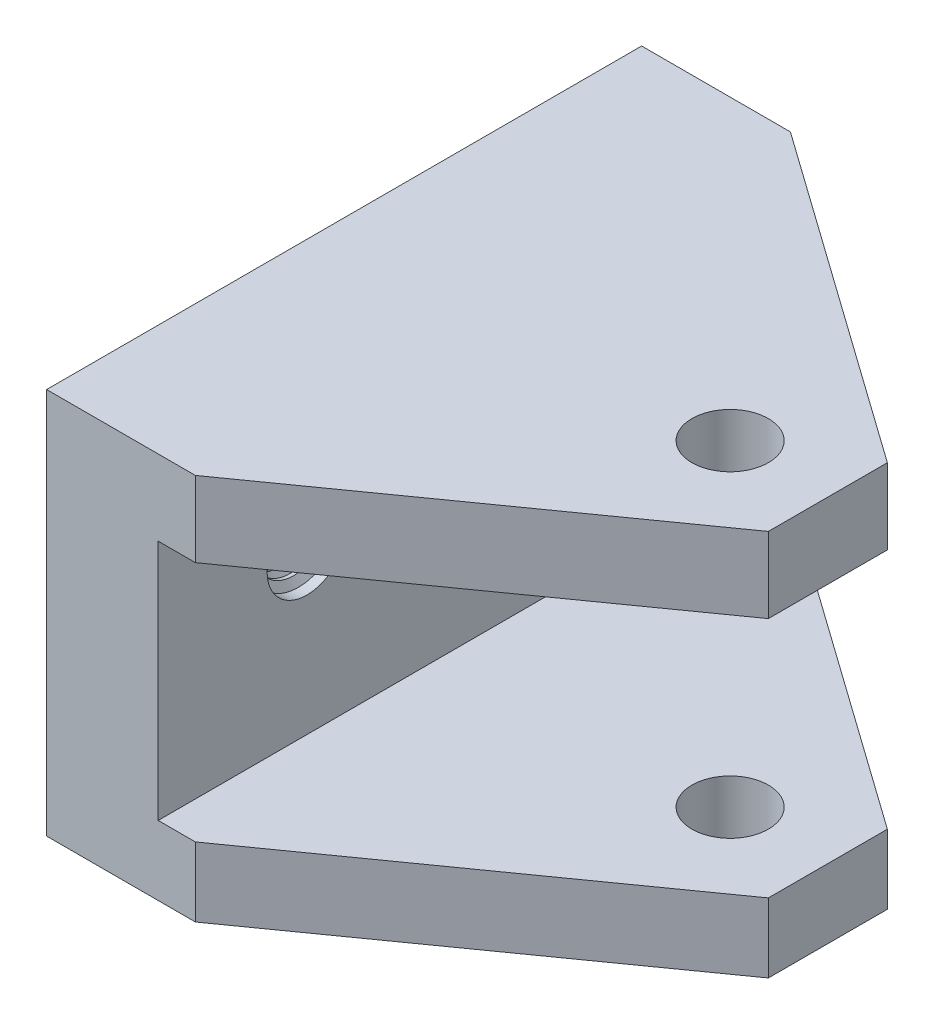
SolidWorks part; units mm, degrees
material "Custom Plastic"
ref_plane "X-Y Datum" through (0, 0, 0) normal (0, 0, 1) x (1, 0, 0)
ref_plane "X-Z Datum" through (0, 0, 0) normal (0, 1, 0) x (1, 0, 0)
ref_plane "Y-Z Datum" through (0, 0, 0) normal (1, 0, 0) x (0, 0, -1)
sketch "Sketch1" plane through (0, 0, 0) normal (0, 0, 1) x (1, 0, 0)
  line L0 (0, 1.7916) -> (0, 34.8116)
  line L1 (0, 34.8116) -> (45.6553, 34.8116)
  line L2 (45.6553, 34.8116) -> (45.6553, 28.3637)
  line L3 (45.6553, 28.3637) -> (9.525, 28.3637)
  line L4 (9.525, 28.3637) -> (9.525, 7.7135)
  line L5 (9.525, 7.7135) -> (45.6553, 7.7135)
  line L6 (45.6553, 7.7135) -> (45.6553, 1.7916)
  line L7 (0, 1.7916) -> (45.6553, 1.7916)
  line L8 (32.9553, 34.8116) -> (32.9553, 1.7916) construction
  line L9 (0, 21.4305) -> (9.525, 21.4305) construction
  line L10 (-200003.822, 21.4305) -> (200058.8771, 21.4305) construction
  line L11 (0, -10.6311) -> (0, 37.657) construction
  circle A0 centre (32.9553, 18.0386) radius 10.3251 construction
  dimension "D3" = 20.6502
  dimension "D1" = 20.6502
  dimension "D2" = 33.02
  dimension "D4" = 12.7
  dimension "D5" = 9.525
extrude "Boss-Extrude1" add sketch "Sketch1" along normal blind 50.8
sketch "Sketch2" plane through (9.525, 0, 0) normal (1, 0, 0) x (0, 0, -1)
  line L0 (-25.4, 28.3637) -> (-25.4, 7.7135) construction
  line L1 (-50.8, 28.3637) -> (0, 28.3637) construction
  line L2 (-50.8, 7.7135) -> (0, 7.7135) construction
  line L3 (-38.1, 21.4305) -> (-12.7, 21.4305) construction
  line L4 (-12.7, 21.4305) -> (0, 21.4305) construction
  line L6 (0, 28.3637) -> (0, 7.7135) construction
  circle A0 centre (-38.1, 21.4305) radius 3.4
  circle A1 centre (-12.7, 21.4305) radius 3.4
  dimension "D1" = 6.8
  dimension "D2" = 25.4
  dimension "D3" = 12.7
extrude "Cut-Extrude1" cut sketch "Sketch2" against normal blind 50.8
sketch "Sketch3" plane through (0, 34.8116, 0) normal (0, 1, 0) x (1, 0, 0)
  line L0 (0, -25.4) -> (45.6553, -25.4) construction
  line L1 (0, -50.8) -> (0, 0) construction
  line L2 (45.6553, -50.8) -> (45.6553, 0) construction
  line L3 (12.7, 0) -> (41.2992, -20.32)
  line L4 (41.2992, -20.32) -> (41.2992, -30.48)
  line L5 (41.2992, -30.48) -> (12.7, -50.8)
  line L6 (45.6553, -50.8) -> (0, -50.8) construction
  line L7 (12.7, -50.8) -> (45.6553, -50.8)
  line L8 (45.6553, -50.8) -> (45.6553, 0)
  line L9 (45.6553, 0) -> (12.7, 0)
  line L10 (45.6553, 0) -> (0, 0) construction
  circle A0 centre (32.9553, -25.4) radius 3.2639
  point P7 (45.6553, -25.4)
  dimension "D1" = 6.5278
  dimension "D5" = 5.08
  dimension "D2" = 12.7
  dimension "D3" = 10.16
  dimension "D4" = 12.7
extrude "Cut-Extrude2" cut sketch "Sketch3" against normal up to surface (33.02 mm away) up to face at (22.8276, 1.7916, 25.4)
thread "Thread1" pitch 1.25 method extrude profile "Thread Profile1" start angle 0, offset 0, length 0, pitch 1.25, diameter 6.8
ref_plane "Plane1" through (9.525, 21.4305, 16.1) normal (0, -1, 0) x (0, 0, 1)
sketch "Thread Profile1" plane through (9.525, 21.4305, 16.1) normal (0, -1, 0) x (0, 0, 1)
  line L0 (0, 0) -> (0, 1.25) construction
  line L11 (0, 0) -> (0, 1.0937)
  line L12 (0, 1.0937) -> (-0.6766, 0.7031)
  line L13 (-0.6766, 0.7031) -> (-0.6766, 0.3906)
  line L15 (-0.6766, 0.3906) -> (0, 0)
  line L17 (-0.6766, 0.5469) -> (0, 0.5469) construction
  point P2 (0, 0)
  dimension "Pitch" = 1.25
  dimension "Profile_Angle" = 60
  dimension "Profile_Land" = 0.3125
  dimension "Profile_Height" = 0.6766
thread "Thread2" pitch 1.25 method extrude profile "Thread Profile2" start angle 0, offset 0, length 0, pitch 1.25, diameter 6.8
ref_plane "Plane2" through (9.525, 21.4305, 41.5) normal (0, -1, 0) x (0, 0, 1)
sketch "Thread Profile2" plane through (9.525, 21.4305, 41.5) normal (0, -1, 0) x (0, 0, 1)
  line L0 (0, 0) -> (0, 1.25) construction
  line L11 (0, 0) -> (0, 1.0937)
  line L12 (0, 1.0937) -> (-0.6766, 0.7031)
  line L13 (-0.6766, 0.7031) -> (-0.6766, 0.3906)
  line L15 (-0.6766, 0.3906) -> (0, 0)
  line L17 (-0.6766, 0.5469) -> (0, 0.5469) construction
  point P2 (0, 0)
  dimension "Pitch" = 1.25
  dimension "Profile_Angle" = 60
  dimension "Profile_Land" = 0.3125
  dimension "Profile_Height" = 0.6766
